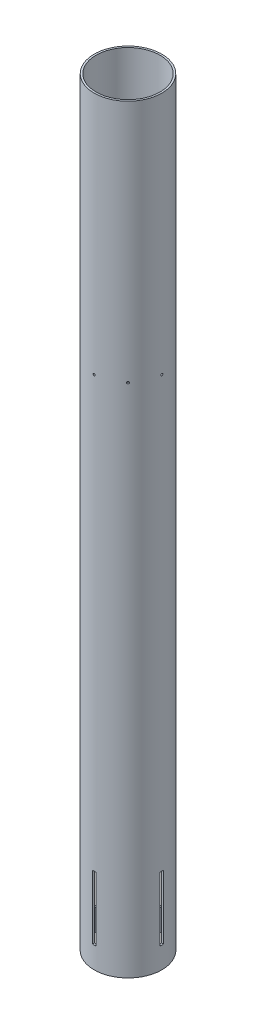
SolidWorks part; units mm, degrees
material "Hexcel AS4C (3000 Filaments)"
ref_plane "Front Plane" through (0, 0, 0) normal (0, 0, 1) x (1, 0, 0)
ref_plane "Top Plane" through (0, 0, 0) normal (0, 1, 0) x (1, 0, 0)
ref_plane "Right Plane" through (0, 0, 0) normal (1, 0, 0) x (0, 0, -1)
sketch "Sketch1" plane through (0, 0, 0) normal (0, 1, 0) x (1, 0, 0)
  circle A0 centre (0, 0) radius 50.8
  dimension "D1" = 101.6
extrude "Body Tube Extrusion" add sketch "Sketch1" along normal blind 1206.5 thin thin type one direction wall 2.921
ref_plane "Plane1" through (0, 0, 53.721) normal (0, 0, 1) x (1, 0, 0)
sketch "Sketch2" plane through (0, 0, 53.721) normal (0, 0, 1) x (1, 0, 0)
  line L0 (0, 1206.5) -> (0, 0) construction
  line L1 (50.8, 1206.5) -> (-50.8, 1206.5) construction
  line L2 (-53.721, 0) -> (53.721, 0) construction
  circle A0 centre (0, 819.15) radius 1.6383
  dimension "D1" = 3.2766
  dimension "D2" = 819.15
extrude "Engine Block Hole" cut sketch "Sketch2" against normal up to next
pattern_circular "CirPattern1" count 8 over 360 about axis through (0, 1206.5, 0) along (0, -1, 0) of "Engine Block Hole"
sketch "Sketch3" plane through (0, 0, 53.721) normal (0, 0, 1) x (1, 0, 0)
  line L0 (0, 0) -> (0, 34.29) construction
  line L1 (-50.8, 0) -> (50.8, 0) construction
  line L2 (0, 1206.5) -> (0, 0) construction
  line L4 (-2.667, 135.89) -> (2.667, 135.89)
  line L5 (-2.667, 135.89) -> (-2.667, 34.29)
  line L6 (-2.667, 34.29) -> (2.667, 34.29)
  line L7 (2.667, 135.89) -> (2.667, 34.29)
  point P10 (0, 34.29)
  dimension "D1" = 101.6
  dimension "D2" = 5.334
  dimension "D3" = 34.29
extrude "Cut-Extrude1" cut sketch "Sketch3" against normal up to next
pattern_circular "CirPattern2" count 4 over 360 about axis through (0, 1206.5, 0) along (0, -1, 0) of "Cut-Extrude1" reverse direction yes
